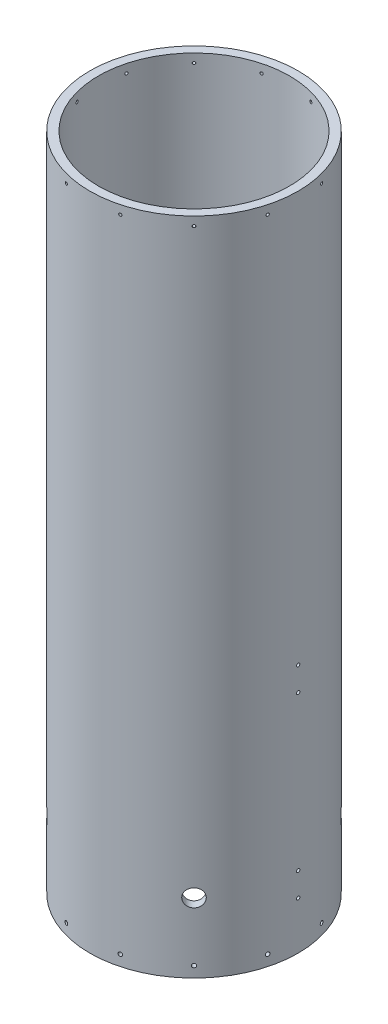
SolidWorks part; units mm, degrees
ref_plane "Front Plane" through (0, 0, 0) normal (0, 0, 1) x (1, 0, 0)
ref_plane "Top Plane" through (0, 0, 0) normal (0, 1, 0) x (1, 0, 0)
ref_plane "Right Plane" through (0, 0, 0) normal (1, 0, 0) x (0, 0, -1)
sketch "Sketch1" plane through (0, 0, 0) normal (0, 1, 0) x (1, 0, 0)
  circle A0 centre (0, 0) radius 152.4
  circle A1 centre (0, 0) radius 139.7
  dimension "D2" = 304.8
  dimension "D1" = 279.4
extrude "Boss-Extrude1" add sketch "Sketch1" along normal blind 965.2
ref_plane "Plane1" through (-152.4, 0, 0) normal (-1, 0, 0) x (0, 0, 1)
ref_plane "Plane2" through (0, 482.6, 0) normal (0, 1, 0) x (1, 0, 0)
hole_wizard "#10 (0.1935) Diameter Hole2" positions "Sketch7" profile "Sketch8" hole size "#10" standard "ANSI Inch" end condition up to next
sketch "Sketch7" plane through (-152.4, 0, 0) normal (-1, 0, 0) x (0, 0, 1)
  line L0 (0, 365.125) -> (0, 330.2)
  line L1 (0, 330.2) -> (0, 0)
  point P0 (0, 365.125)
  point P2 (0, 330.2)
  point P11 (0, 104.775)
  point P13 (0, 69.85)
  dimension "D1" = 34.925
  dimension "D2" = 330.2
  dimension "D3" = 34.925
  dimension "D4" = 260.35
sketch "Sketch8" plane through (-152.4, 365.125, 0) normal (0, 1, 0) x (0, 0, 1)
  line L0 (0, 0) -> (0, 304.8)
  line L1 (0, 304.8) -> (2.4574, 304.8)
  line L2 (2.4574, 304.8) -> (2.4574, 0)
  line L5 (2.4574, 0) -> (0, 0)
  line L11 (0, -6.35) -> (0, 107.95) construction
  dimension "Thru Hole Dia." = 4.9149
  dimension "Thru Hole Depth" = 304.8
pattern_circular "CirPattern2" count 2 over 360 about axis through (0, 965.2, 0) along (0, 1, 0) of "#10 (0.1935) Diameter Hole2"
ref_plane "Plane3" through (-107.7631, 0, -107.7631) normal (-0.7071, 0, -0.7071) x (0, -1, 0)
hole_wizard "Tap Drill for #10-32 Tap1" positions "Sketch10" profile "Sketch11" hole size "#10-32" standard "ANSI Inch" end condition up to next
sketch "Sketch10" plane through (-107.7631, 0, -107.7631) normal (-0.7071, 0, -0.7071) x (0, -1, 0)
  line L0 (-965.2, 139.7) -> (-965.2, -139.7) construction
  point P0 (-952.5, 0)
  dimension "D1" = 12.7
sketch "Sketch11" plane through (-107.7631, 952.5, -107.7631) normal (0, 1, 0) x (-0.7071, 0, 0.7071)
  line L0 (0, 0) -> (0, 323.4981)
  line L1 (0, 323.4981) -> (2.0193, 323.4981)
  line L2 (2.0193, 323.4981) -> (2.0193, 0)
  line L5 (2.0193, 0) -> (0, 0)
  line L11 (0, -6.35) -> (0, 107.95) construction
  dimension "Thru Hole Dia." = 4.0386
  dimension "Thru Hole Depth" = 323.4981
pattern_circular "CirPattern3" count 12 over 360 about axis through (0, 965.2, 0) along (0, -1, 0) of "Tap Drill for #10-32 Tap1"
sketch "Sketch12" plane through (-107.7631, 0, -107.7631) normal (-0.7071, 0, -0.7071) x (0, -1, 0)
  line L0 (0, -152.4) -> (0, 152.4) construction
  circle A0 centre (-101.6, 0) radius 12.7
  dimension "D1" = 25.4
  dimension "D2" = 101.6
extrude "Cut-Extrude1" cut sketch "Sketch12" against normal up to next
pattern_circular "CirPattern4" count 4 over 360 about axis through (0, 965.2, 0) along (0, -1, 0) of "Cut-Extrude1"
ref_plane "Plane4" through (0, 0, -152.4) normal (0, 0, -1) x (0, -1, 0)
sketch "Sketch13" plane through (0, 0, -152.4) normal (0, 0, -1) x (0, -1, 0)
  line L0 (0, -152.4) -> (0, 152.4) construction
  circle A0 centre (-228.6, 0) radius 12.7
  dimension "D1" = 25.4
  dimension "D2" = 228.6
extrude "Cut-Extrude2" cut sketch "Sketch13" against normal up to next
hole_wizard "#10 Clearance Hole2" positions "Sketch14" profile "Sketch15" hole size "#10" standard "ANSI Inch" end condition up to next
sketch "Sketch14" plane through (-107.7631, 0, -107.7631) normal (-0.7071, 0, -0.7071) x (0, -1, 0)
  line L0 (0, -152.4) -> (0, 152.4) construction
  point P0 (-15.875, 0)
  dimension "D1" = 15.875
sketch "Sketch15" plane through (-107.7631, 15.875, -107.7631) normal (0, 1, 0) x (-0.7071, 0, 0.7071)
  line L0 (0, 0) -> (0, 323.4981)
  line L1 (0, 323.4981) -> (2.8067, 323.4981)
  line L2 (2.8067, 323.4981) -> (2.8067, 0)
  line L5 (2.8067, 0) -> (0, 0)
  line L11 (0, -6.35) -> (0, 107.95) construction
  dimension "Thru Hole Dia." = 5.6134
  dimension "Thru Hole Depth" = 323.4981
pattern_circular "CirPattern5" count 12 over 360 about axis through (0, 965.2, 0) along (0, -1, 0) of "#10 Clearance Hole2"
